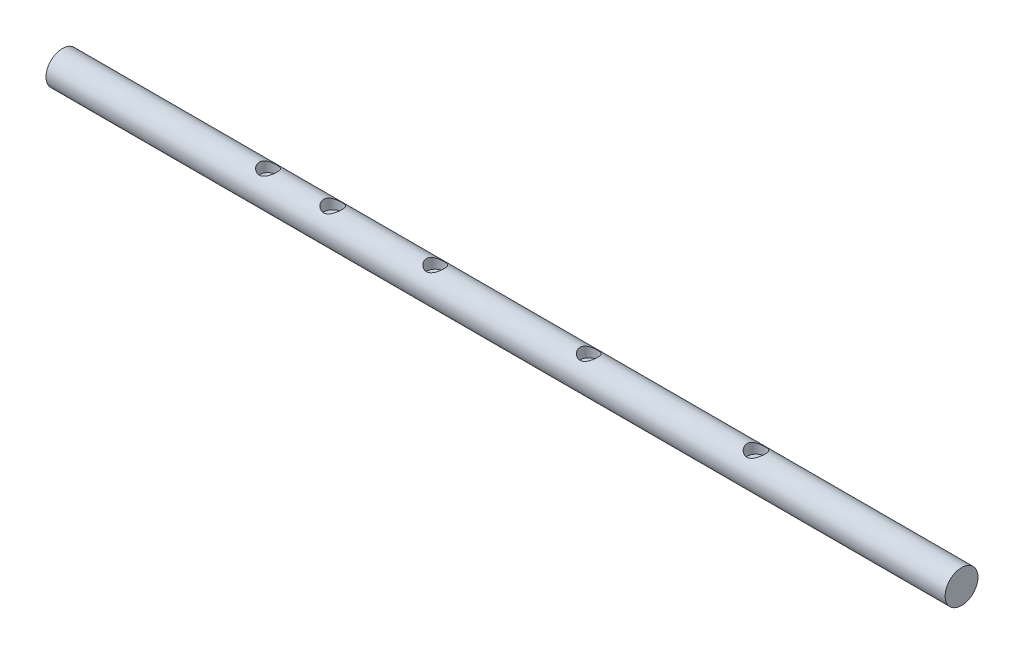
SolidWorks part; units mm, degrees
ref_plane "Ön Düzlem" through (0, 0, 0) normal (0, 0, 1) x (1, 0, 0)
ref_plane "Üst Düzlem" through (0, 0, 0) normal (0, 1, 0) x (1, 0, 0)
ref_plane "Sağ Düzlem" through (0, 0, 0) normal (1, 0, 0) x (0, 0, -1)
sketch "Sketch1" plane through (0, 0, 0) normal (0, 0, 1) x (1, 0, 0)
  line L1 (-147.6159, 1.1591) -> (16.3841, 1.1591)
  line L2 (-147.6159, 1.1591) -> (-147.6159, -1.8409)
  line L3 (-147.6159, -1.8409) -> (16.3841, -1.8409)
  line L4 (16.3841, 1.1591) -> (16.3841, -1.8409)
  dimension "D1" = 3
  dimension "D2" = 164
revolve "Revolve1" add sketch "Sketch1" angle 360 about L1
sketch "Sketch2" plane through (16.3841, 0, 0) normal (1, 0, 0) x (0, 0, -1)
  line L0 (0, 1.1591) -> (0, 4.1591)
  circle A0 centre (0, 1.1591) radius 3 construction
ref_plane "Plane1" through (16.3841, 4.1591, 0) normal (0, 1, 0) x (1, 0, 0)
sketch "Sketch3" plane through (16.3841, 4.1591, 0) normal (0, 1, 0) x (1, 0, 0)
  line L0 (-164, 0) -> (-137, 0)
  line L1 (-164, 3) -> (-164, -3) construction
  line L2 (0, 0) -> (-27, 0)
  line L3 (0, -3) -> (0, 3) construction
  line L4 (-27, 0) -> (-35, 0)
  line L5 (-137, 0) -> (-129, 0)
  line L6 (-129, 0) -> (-126.5, 0)
  line L7 (-35, 0) -> (-37.5, 0)
  line L8 (-129, 0) -> (-114.7, 0)
  line L9 (-35, 0) -> (-68, 0)
  line L10 (-68, 0) -> (-96, 0)
  circle A0 centre (-114.7, 0) radius 1.65
  circle A1 centre (-126.5, 0) radius 1.6
  circle A2 centre (-37.5, 0) radius 1.65
  circle A3 centre (-68, 0) radius 1.6
  circle A4 centre (-96, 0) radius 1.6
  dimension "D8" = 3.3
  dimension "D9" = 3.2
  dimension "D10" = 3.3
  dimension "D13" = 3.2
  dimension "D14" = 3.2
  dimension "D1" = 27
  dimension "D2" = 27
  dimension "D3" = 8
  dimension "D4" = 8
  dimension "D5" = 2.5
  dimension "D6" = 2.5
  dimension "D7" = 14.3
  dimension "D11" = 33
  dimension "D12" = 28
extrude "Cut-Extrude3" cut sketch "Sketch3" against normal blind 2 contours L8 A1 | L8 A1 | A0 | A4 | L9 A3 L10 | L10 A3 L9 | L9 A2 | L9 A2 region at (-110.1159, 4.1591, -0.6791) region at (-98.3159, 4.1591, -1.6033) region at (-110.1159, 4.1591, 0.6791) region at (-21.1159, 4.1591, 0.7003) region at (-21.1159, 4.1591, -0.7003) region at (-81.1706, 4.1591, 0) region at (-51.6159, 4.1591, 0.6791) region at (-51.6159, 4.1591, -0.6791)
